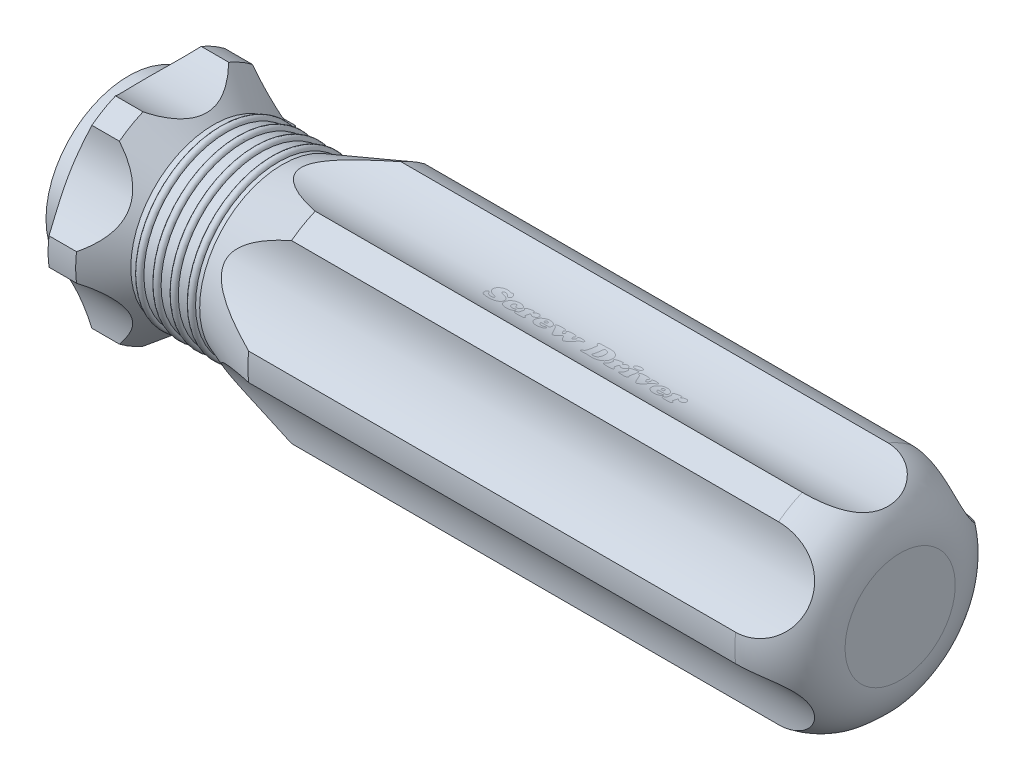
SolidWorks part; units mm, degrees
ref_plane "Front Plane" through (0, 0, 0) normal (0, 0, 1) x (1, 0, 0)
ref_plane "Top Plane" through (0, 0, 0) normal (0, 1, 0) x (1, 0, 0)
ref_plane "Right Plane" through (0, 0, 0) normal (1, 0, 0) x (0, 0, -1)
sketch "Sketch1" plane through (0, 0, 0) normal (0, 0, 1) x (1, 0, 0)
  line L0 (0, 6) -> (1, 6)
  line L1 (0, 0) -> (56, 0)
  line L2 (0, 0) -> (0, 8) construction
  line L3 (0, 8) -> (56, 8) construction
  line L4 (56, 0) -> (56, 4)
  line L5 (1, 6) -> (2.1547, 8)
  line L6 (2.1547, 8) -> (4.1547, 8)
  line L7 (4.1547, 8) -> (6.1547, 6)
  line L8 (6.1547, 6) -> (11.1547, 6)
  line L9 (11.1547, 6) -> (16.6497, 8)
  line L10 (16.6497, 8) -> (52, 8)
  line L11 (0, 6) -> (0, 0)
  arc A0 (52, 8) -> (56, 4) centre (52, 4) cw
  dimension "D10" = 4
  dimension "D1" = 56
  dimension "D2" = 8
  dimension "D3" = 1
  dimension "D4" = 120
  dimension "D5" = 2
  dimension "D6" = 2
  dimension "D7" = 5
  dimension "D8" = 135
  dimension "D9" = 20
revolve "Revolve1" add sketch "Sketch1" angle 360 about L1
sketch "Sketch2" plane through (0, 0, 0) normal (0, 0, 1) x (1, 0, 0)
  line L0 (11.1547, 6) -> (6.1547, 6) construction
  line L1 (6.1547, 6) -> (6.1547, -6) construction
  line L2 (0, 0) -> (56, 0) construction
  line L3 (56, -4) -> (56, 4) construction
  circle A0 centre (6.8547, 6) radius 0.25
  dimension "D1" = 0.5
  dimension "D2" = 0.7
revolve "Revolve2" add sketch "Sketch2" angle 360 about L2
pattern_linear "LPattern1" count 4 spacing 1.25 along (1, 0, 0) of "Revolve2"
sketch "Sketch3" plane through (0, 0, 0) normal (-1, 0, 0) x (0, 0, 1)
  circle A1 centre (0, 12.5) radius 6
  point P2 (0, 0)
  dimension "D1" = 12
  dimension "D2" = 12.5
extrude "Cut-Extrude1" cut sketch "Sketch3" against normal through all
pattern_circular "CirPattern1" count 6 over 360 about axis through (0, 0, 0) along (-1, 0, 0) of "Cut-Extrude1"
sketch "Sketch4" plane through (0, 0, 0) normal (0, 1, 0) x (1, 0, 0)
  line L0 (13.6579, -1.6118) -> (54.7433, -1.6118) construction
  line L1 (52, -3.1118) -> (16.6497, -3.1118) construction
  spline S0 degree 3 poles (16.6497, -3.1118) (16.2326, -2.9516) (15.8193, -2.7809) (15.0048, -2.4075) (14.603, -2.2052) (14.0241, -1.8614) (13.835, -1.7399) (13.4692, -1.4752) (13.2926, -1.3324) (12.969, -1.0151) (12.8213, -0.8402) (12.5992, -0.4463) (12.5261, -0.2185) (12.5309, 0.2425) (12.6072, 0.4663) (12.779, 0.7618) (12.8463, 0.8557) (12.9906, 1.0309) (13.068, 1.1132) (13.3115, 1.3485) (13.4895, 1.491) (13.8549, 1.7531) (14.0432, 1.8732) (14.6183, 2.2131) (15.0153, 2.4126) (15.8232, 2.7825) (16.2349, 2.9525) (16.6497, 3.1118) knots 0 0 0 0 0.125 0.125 0.25 0.25 0.3125 0.3125 0.375 0.375 0.4375 0.4375 0.5 0.5 0.5625 0.5625 0.59375 0.59375 0.625 0.625 0.6875 0.6875 0.75 0.75 0.875 0.875 1 1 1 1 construction
  spline S1 degree 3 poles (52, 3.1118) (52.2124, 3.1118) (52.4214, 3.0942) (52.8329, 3.0241) (53.0375, 2.9706) (53.4259, 2.8284) (53.6099, 2.7402) (53.9567, 2.5257) (54.1191, 2.3988) (54.4058, 2.116) (54.5329, 1.9583) (54.7523, 1.6111) (54.8413, 1.4272) (54.9833, 1.04) (55.0363, 0.835) (55.1054, 0.4225) (55.1224, 0.2134) (55.1226, -0.2108) (55.1055, -0.4207) (55.037, -0.8318) (54.9846, -1.0359) (54.8424, -1.4247) (54.7538, -1.6079) (54.5378, -1.9513) (54.4087, -2.1127) (54.1216, -2.3967) (53.9627, -2.5215) (53.6133, -2.7385) (53.428, -2.8275) (53.0404, -2.9698) (52.8356, -3.0235) (52.4221, -3.0942) (52.2125, -3.1118) (52, -3.1118) knots 0 0 0 0 0.0625 0.0625 0.125 0.125 0.1875 0.1875 0.25 0.25 0.3125 0.3125 0.375 0.375 0.4375 0.4375 0.5 0.5 0.5625 0.5625 0.625 0.625 0.6875 0.6875 0.75 0.75 0.8125 0.8125 0.875 0.875 0.9375 0.9375 1 1 1 1 construction
  text T0 "Screw Driver" font "Cooper Black" height in points 6
  dimension "D1" = 1.5
wrap "Wrap1" sketch "Sketch4" wrap type scribe source sketch "Sketch4" face at (34.0753, 6.9351, 0.0201)
sketch "Sketch5" plane through (0, 0, 0) normal (-1, 0, 0) x (0, 0, 1)
  circle A0 centre (0, 0) radius 1.5
  dimension "D1" = 3
extrude "Cut-Extrude2" cut sketch "Sketch5" against normal blind 30
